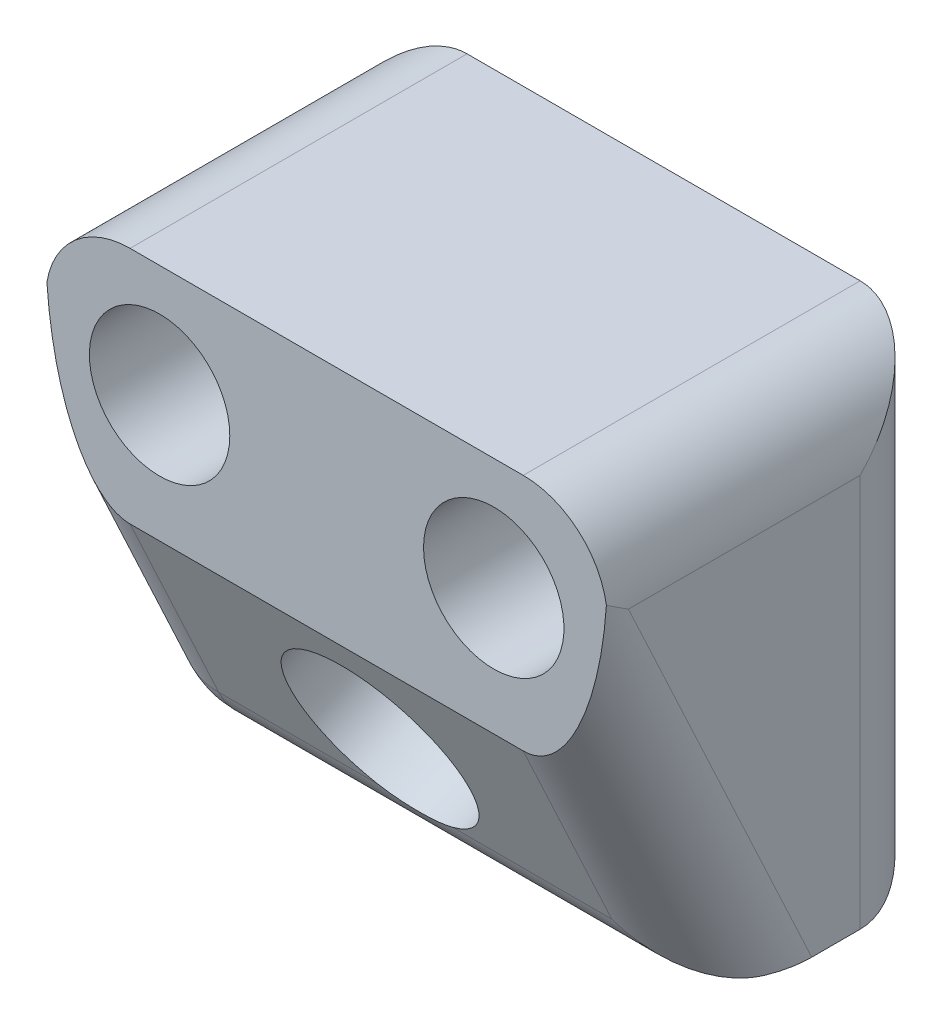
SolidWorks part; units mm, degrees
ref_plane "Alzado" through (0, 0, 0) normal (0, 0, 1) x (1, 0, 0)
ref_plane "Planta" through (0, 0, 0) normal (0, 1, 0) x (1, 0, 0)
ref_plane "Vista lateral" through (0, 0, 0) normal (1, 0, 0) x (0, 0, -1)
sketch "Croquis1" plane through (0, 0, 0) normal (0, 0, 1) x (1, 0, 0)
  line L1 (-44.4644, 14.6457) -> (-24.4644, 14.6457)
  line L2 (-44.4644, 14.6457) -> (-44.4644, -2.3543)
  line L3 (-44.4644, -2.3543) -> (-24.4644, -2.3543)
  line L4 (-24.4644, 14.6457) -> (-24.4644, -2.3543)
  line L5 (-44.4644, 14.6457) -> (-24.4644, -2.3543) construction
  line L6 (-44.4644, -2.3543) -> (-24.4644, 14.6457) construction
  line L7 (-42.9144, 10.6457) -> (-40.4144, 10.6457) construction
  line L8 (-34.4644, 6.1457) -> (-34.4644, 14.6457) construction
  circle A0 centre (-40.4144, 10.6457) radius 2.5
  circle A1 centre (-28.5144, 10.6457) radius 2.5
  point P0 (-34.4644, 6.1457)
  dimension "D1" = 20
  dimension "D2" = 17
  dimension "D4" = 2.5
  dimension "D5" = 4
  dimension "D6" = 5.95
extrude "Saliente-Extruir2" add sketch "Croquis1" along normal blind 12
sketch "Croquis4" plane through (-24.4644, 0, 0) normal (1, 0, 0) x (0, 0, -1)
  line L1 (-12, -2.3543) -> (-12, 14.6457) construction
  line L4 (-12, 6.1457) -> (-8.0364, -2.3543)
  line L5 (-12, -2.3543) -> (0, -2.3543) construction
  line L6 (-8.0364, -2.3543) -> (-12, -2.3543)
  line L7 (-12, -2.3543) -> (-12, 6.1457)
  dimension "D1" = 25
extrude "Cortar-Extruir2" cut sketch "Croquis4" against normal up to vertex (20 mm away) up to point (-44.4644, -2.3543, 12)
sketch "Croquis5" plane through (0, 11.802, 14.6376) normal (0, 0.4226, -0.9063) x (1, 0, 0)
  line L0 (-34.4644, 6.2411) -> (-34.4644, 10.7411) construction
  line L2 (-44.4644, 6.2411) -> (-24.4644, 6.2411) construction
  circle A1 centre (-34.4644, 10.7411) radius 3.25
extrude "Cortar-Extruir3" cut sketch "Croquis5" along normal blind 20
sketch "Croquis6" plane through (0, 11.802, 14.6376) normal (0, 0.4226, -0.9063) x (1, 0, 0)
  line L13 (-29.6147, 10.7411) -> (-32.0396, 14.9411)
  line L14 (-32.0396, 14.9411) -> (-36.8893, 14.9411)
  line L15 (-36.8893, 14.9411) -> (-39.3142, 10.7411)
  line L16 (-39.3142, 10.7411) -> (-36.8893, 6.5411)
  line L17 (-36.8893, 6.5411) -> (-32.0396, 6.5411)
  line L18 (-32.0396, 6.5411) -> (-29.6147, 10.7411)
  circle A0 centre (-34.4644, 10.7411) radius 4.2 construction
  dimension "D1" = 8.4
extrude "Cortar-Extruir4" cut sketch "Croquis6" along normal blind 20 from offset 4
fillet "Redondeo1" radius 3 9 edges at (-44.4644, 6.1457, 0) (-44.4644, 14.6457, 6) (-24.4644, 14.6457, 6) (-24.4644, 6.1457, 0) (-34.4644, -2.3543, 0) (-44.4644, -2.3543, 4.0182) (-44.4644, 1.8957, 10.0182) (-24.4644, 1.8957, 10.0182) (-34.4644, -2.3543, 8.0364)
